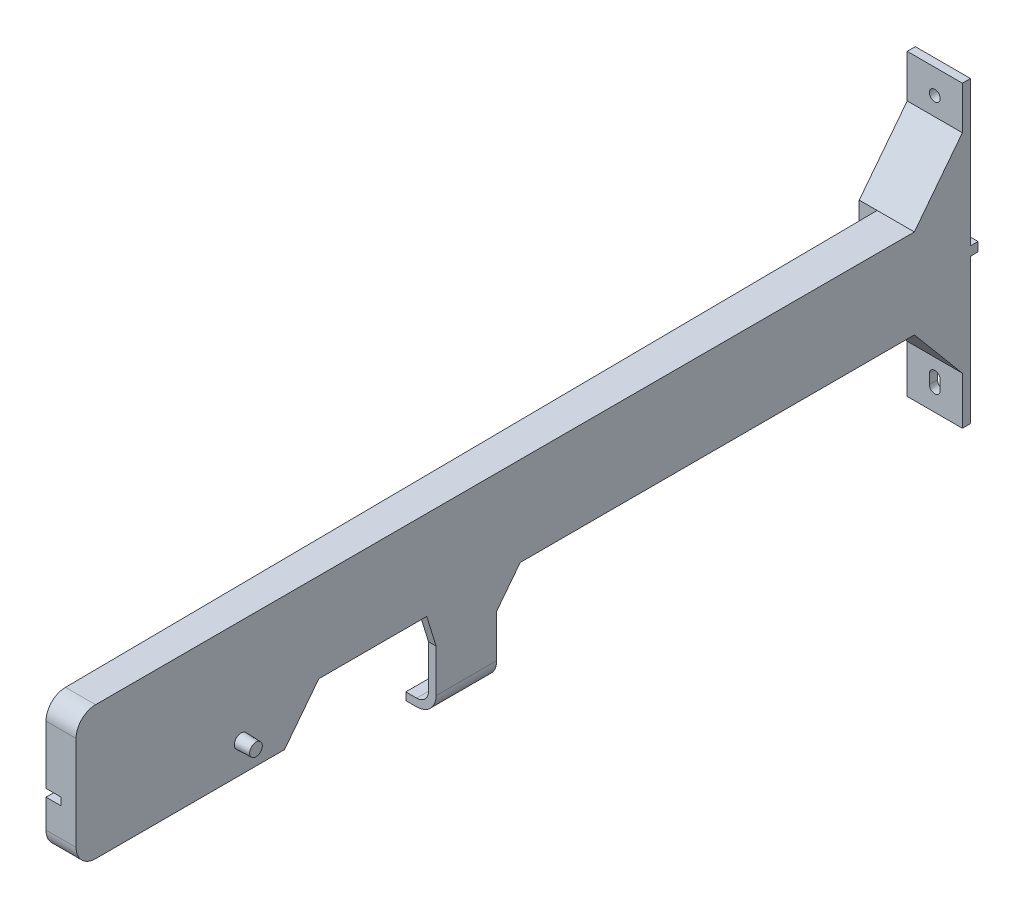
SolidWorks part; units mm, degrees
ref_plane "Front Plane" through (0, 0, 0) normal (0, 0, 1) x (1, 0, 0)
ref_plane "Top Plane" through (0, 0, 0) normal (0, 1, 0) x (1, 0, 0)
ref_plane "Right Plane" through (0, 0, 0) normal (1, 0, 0) x (0, 0, -1)
sketch "Sketch1" plane through (0, 0, 0) normal (1, 0, 0) x (0, 0, -1)
  line L0 (199.075, 43.925) -> (199.075, -81.275)
  line L1 (199.075, -81.275) -> (195.675, -81.275)
  line L2 (195.675, -81.275) -> (195.675, -61.275)
  line L3 (195.675, -61.275) -> (175.575, -37.35)
  line L4 (175.575, -37.35) -> (10.475, -37.35)
  line L5 (10.475, -37.35) -> (0.6285, -50.05)
  line L6 (0.6285, -50.05) -> (0.6285, -76.2)
  line L7 (0.6285, -76.2) -> (-24.7715, -76.2)
  line L8 (-24.7715, -76.2) -> (-24.7715, -50.05)
  line L9 (-24.7715, -50.05) -> (-28.6864, -37.35)
  line L10 (-28.6864, -37.35) -> (-73.9049, -37.35)
  line L11 (-73.9049, -37.35) -> (-88.2715, -55.88)
  line L12 (-88.2715, -55.88) -> (-175.575, -55.88)
  line L13 (-175.575, -55.88) -> (-175.575, 0)
  line L14 (-175.575, 0) -> (175.575, 0)
  line L17 (195.675, 43.925) -> (199.075, 43.925)
  line L18 (175.575, 0) -> (195.675, 25.925)
  line L19 (195.675, 25.925) -> (195.675, 43.925)
  line L20 (175.575, 0) -> (175.575, -37.35)
  line L21 (-28.6864, -37.35) -> (10.475, -37.35)
  line L22 (-24.7715, -73.025) -> (0.6285, -73.025)
  line L23 (175.575, 0) -> (175.575, -37.35) construction
  point P20 (-12.0715, -76.2)
  point P22 (175.575, -18.675)
  point P23 (0, 0)
  point P25 (199.075, -18.675)
  dimension "D1" = 374.65
  dimension "D2" = 37.35
  dimension "D3" = 23.5
  dimension "D4" = 3.4
  dimension "D5" = 125.2
  dimension "D6" = 20
  dimension "D7" = 55.88
  dimension "D8" = 76.2
  dimension "D9" = 165.1
  dimension "D10" = 63.5
  dimension "D11" = 25.4
  dimension "D12" = 12.7
  dimension "D13" = 3.175
  dimension "D14" = 18
extrude "Boss-Extrude1" add sketch "Sketch1" against normal blind 12.6 contours L20 L14 L13 L12 L11 L10 L9 L8 L7 L6 L5 L4 region at (0, -21.9379, 15.1032)
extrude "Boss-Extrude2" add sketch "Sketch1<3>" against normal blind 23.1 contours L18 L20 L3 L2 L1 L0 L17 L19 region at (0, -18.2521, -189.6074)
sketch "Sketch1<3>" plane through (0, 0, 0) normal (1, 0, 0) x (0, 0, -1) same geometry as "Sketch1"
extrude "Boss-Extrude3" add sketch "Sketch1<4>" against normal blind 3.175 contours L8 L22 L6 L5 L21 L9 region at (0, -53.991, 11.4161)
sketch "Sketch1<4>" plane through (0, 0, 0) normal (1, 0, 0) x (0, 0, -1) same geometry as "Sketch1"
extrude "Boss-Extrude4" add sketch "Sketch1<5>" against normal blind 12.7 contours L22 L8 L7 L6 region at (0, -74.6125, 12.0715)
sketch "Sketch1<5>" plane through (0, 0, 0) normal (1, 0, 0) x (0, 0, -1) same geometry as "Sketch1"
fillet "Fillet1" radius 5 1 edges at (-3.175, -73.025, 12.0715)
fillet "Fillet2" radius 8.175 3 edges at (-6.3, 0, 175.575) (-6.3, -55.88, 175.575) (0, -76.2, 12.0715)
sketch "Sketch2" plane through (-12.6, 0, 0) normal (-1, 0, 0) x (0, 0, 1)
  line L0 (-131.125, -34.175) -> (222.402, -34.175) construction
  line L1 (-131.125, -32.5875) -> (222.402, -32.5875)
  line L2 (-131.125, -35.7625) -> (222.402, -35.7625)
  line L3 (-175.575, -37.35) -> (73.9049, -37.35) construction
  line L4 (-175.575, 0) -> (-175.575, -37.35) construction
  arc A0 (-131.125, -32.5875) -> (-131.125, -35.7625) centre (-131.125, -34.175) ccw
  arc A1 (222.402, -35.7625) -> (222.402, -32.5875) centre (222.402, -34.175) ccw
  point P2 (45.6385, -34.175)
  dimension "D1" = 1.5875
  dimension "D2" = 1.5875
  dimension "D3" = 44.45
extrude "Cut-Extrude1" cut sketch "Sketch2" against normal blind 6.35
sketch "Sketch3" plane through (0, 0, -199.075) normal (0, 0, -1) x (-1, 0, 0)
  line L0 (11.55, -72.325) -> (11.55, -68.275) construction
  line L1 (9.3, -72.325) -> (9.3, -68.275)
  line L2 (13.8, -72.325) -> (13.8, -68.275)
  line L3 (23.1, -81.275) -> (0, -81.275) construction
  line L4 (23.1, 43.925) -> (0, 43.925) construction
  line L5 (11.55, 33.65) -> (11.55, 35.925) construction
  line L6 (11.55, -70.3) -> (9.3, -70.3) construction
  line L7 (11.55, 33.65) -> (9.275, 33.65) construction
  arc A0 (9.3, -72.325) -> (13.8, -72.325) centre (11.55, -72.325) ccw
  arc A1 (13.8, -68.275) -> (9.3, -68.275) centre (11.55, -68.275) ccw
  circle A2 centre (11.55, 33.65) radius 2.275
  point P2 (11.55, -70.3)
  point P7 (11.55, -74.575)
  point P8 (11.55, -66.025)
  point P12 (11.55, -81.275)
  point P17 (11.55, 43.925)
  dimension "D4" = 4.55
  dimension "D1" = 4.5
  dimension "D2" = 8.55
  dimension "D3" = 6.7
  dimension "D5" = 8
extrude "Cut-Extrude2" cut sketch "Sketch3" against normal up to next
sketch "Sketch4" plane through (0, 0, -199.075) normal (0, 0, -1) x (-1, 0, 0)
  line L0 (23.1, -18.675) -> (0, -18.675)
  line L1 (23.1, 43.925) -> (23.1, -81.275) construction
  line L2 (0, 43.925) -> (0, -81.275) construction
  line L3 (11.55, -56.9) -> (11.55, 19.55)
  point P9 (11.55, -18.675)
  dimension "D1" = 76.45
extrude "Extrude-Thin1" add sketch "Sketch4" along normal blind 3.15 thin thin type mid plane wall 3.8
ref_plane "Plane1" through (0, -70.3, 0) normal (0, -1, 0) x (1, 0, 0)
sketch "Sketch5" plane through (0, 0, 0) normal (1, 0, 0) x (0, 0, -1)
  line L2 (-106.425, -43.625) -> (-106.425, -46.5) construction
  line L3 (-167.4, 0) -> (175.575, 0) construction
  circle A0 centre (-106.425, -43.625) radius 2.875
  point P6 (0, 0)
  dimension "D2" = 5.75
  dimension "D1" = 282
  dimension "D3" = 46.5
extrude "Boss-Extrude5" add sketch "Sketch5" along normal blind 6.2 draft 2
sketch "Sketch6" plane through (0, 0, 0) normal (0, 1, 0) x (1, 0, 0)
  line L0 (-12.6, 175.575) -> (-15.6, 175.575)
  line L1 (-23.1, 175.575) -> (-12.6, 175.575) construction
  line L2 (-15.6, 175.575) -> (-12.6, -167.4)
  line L3 (-12.6, -167.4) -> (-12.6, 175.575)
  point P7 (0, 0)
  point P8 (-12.6, -167.4)
  dimension "D1" = 3
extrude "Boss-Extrude6" add sketch "Sketch6" against normal blind 3.28
